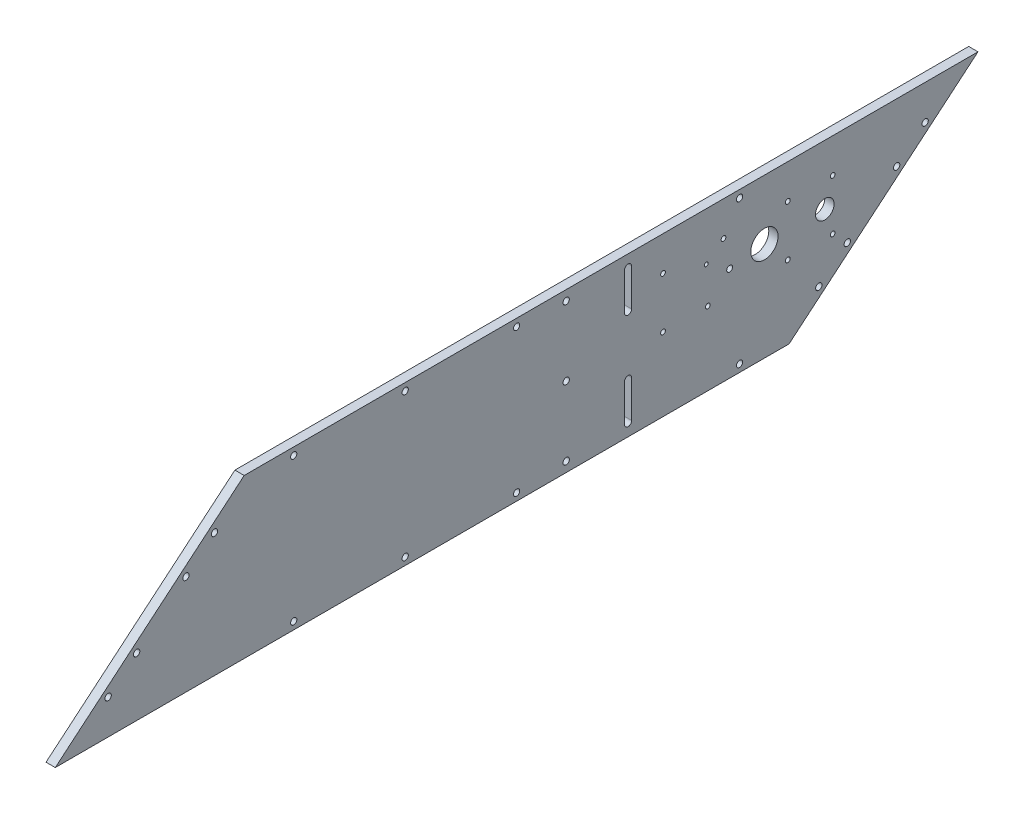
SolidWorks part; units mm, degrees
material "6061-T6 (SS)"
ref_plane "Front Plane" through (0, 0, 0) normal (0, 0, 1) x (1, 0, 0)
ref_plane "Top Plane" through (0, 0, 0) normal (0, 1, 0) x (1, 0, 0)
ref_plane "Right Plane" through (0, 0, 0) normal (1, 0, 0) x (0, 0, -1)
sketch "Sketch1" plane through (0, 0, 0) normal (1, 0, 0) x (0, 0, -1)
  line L0 (0, 12.7) -> (0, -12.7) construction
  line L1 (0, -12.7) -> (33.2976, -40.64) construction
  line L2 (33.2976, -40.64) -> (312.6976, -40.64)
  line L3 (312.6976, -40.64) -> (345.9952, -12.7)
  line L4 (345.9952, -12.7) -> (345.9952, 12.7) construction
  line L5 (345.9952, 12.7) -> (312.6976, 40.64) construction
  line L6 (312.6976, 40.64) -> (33.2976, 40.64)
  line L7 (33.2976, 40.64) -> (0, 12.7)
  line L8 (33.2976, 40.64) -> (33.2976, -40.64) construction
  line L9 (312.6976, 40.64) -> (312.6976, -40.64) construction
  line L10 (0, 0) -> (345.9952, 0) construction
  line L11 (0, 12.7) -> (-63.5681, -40.64)
  line L12 (-63.5681, -40.64) -> (33.2976, -40.64)
  line L13 (312.6976, 40.64) -> (409.5633, 40.64)
  line L14 (409.5633, 40.64) -> (345.9952, -12.7)
  point P10 (33.2976, 0)
  point P12 (312.6976, 0)
  dimension "D1" = 81.28
  dimension "D2" = 279.4
  dimension "D3" = 25.4
  dimension "D4" = 40
extrude "Boss-Extrude1" add sketch "Sketch1" along normal blind 4.7625
sketch "Sketch2" plane through (4.7625, 0, 0) normal (1, 0, 0) x (0, 0, -1)
  line L0 (-3.2177, 10) -> (373.048, 10) construction
  line L1 (312.6976, -40.64) -> (409.5633, 40.64) construction
  line L2 (345.048, 10) -> (245.048, 10) construction
  line L3 (245.048, -5) -> (345.048, -5) construction
  line L4 (245.048, -5) -> (245.048, 25) construction
  line L5 (245.048, 25) -> (345.048, 25) construction
  line L6 (345.048, -5) -> (345.048, 25) construction
  line L7 (0, 0) -> (361.1305, 0) construction
  line L9 (33.2976, 40.64) -> (-63.5681, -40.64) construction
  circle A0 centre (300.048, 10) radius 6.9977
  circle A1 centre (282.2147, 8) radius 1.4986
  circle A2 centre (270.2178, 15.9334) radius 0.9906
  circle A3 centre (282.2147, 8) radius 11.4777 construction
  circle A4 centre (270.2178, 15.9334) radius 7.1501 construction
  circle A5 centre (300.048, 10) radius 12.827 construction
  circle A6 centre (261.048, 10) radius 14 construction
  circle A7 centre (282.2147, 8) radius 5.1181 construction
  circle A8 centre (331.0042, 10) radius 4.7625
  point P11 (300.048, 10)
  point P12 (282.2147, 8)
  point P13 (270.2178, 15.9334)
  point P23 (261.048, 10)
  dimension "D5" = 13.9954
  dimension "D6" = 2.9972
  dimension "D7" = 1.9812
  dimension "D8" = 25.654
  dimension "D9" = 22.9553
  dimension "D10" = 14.3002
  dimension "D12" = 28
  dimension "D13" = 10.2362
  dimension "D17" = 9.525
  dimension "D1" = 17.9451
  dimension "D2" = 14.3828
  dimension "D3" = 30
  dimension "D4" = 100
  dimension "D11" = 10.922
  dimension "D14" = 16
  dimension "D15" = 13
  dimension "D16" = 55
  dimension "D18" = 30.9562
  dimension "D19" = 28
  dimension "D20" = 10
extrude "Gearbox (with Press fits)" cut sketch "Sketch2" against normal through all
sketch "Sketch6" plane through (4.7625, 0, 0) normal (1, 0, 0) x (0, 0, -1)
  line L0 (0, 0) -> (361.1305, 0) construction
  line L1 (230.1476, 36.83) -> (230.1476, -36.83) construction
  line L2 (28.757, 36.83) -> (405.0227, 36.83) construction
  line L3 (33.2976, 40.64) -> (-63.5681, -40.64) construction
  line L4 (230.1476, 34.29) -> (230.1476, 15.24) construction
  line L5 (409.5633, 40.64) -> (33.2976, 40.64) construction
  line L6 (312.6976, -40.64) -> (409.5633, 40.64) construction
  line L7 (231.9764, 34.29) -> (231.9764, 15.24)
  line L8 (228.3188, 34.29) -> (228.3188, 15.24)
  line L9 (409.5633, 40.64) -> (33.2976, 40.64) construction
  line L10 (230.1476, -34.29) -> (230.1476, -15.24) construction
  line L11 (231.9764, -34.29) -> (231.9764, -15.24)
  line L12 (228.3188, -34.29) -> (228.3188, -15.24)
  circle A0 centre (287.2976, 36.83) radius 1.5939
  circle A1 centre (230.1476, 36.83) radius 1.5939 construction
  circle A2 centre (172.9976, 36.83) radius 1.5939
  circle A3 centre (115.8476, 36.83) radius 1.5938
  circle A4 centre (58.6976, 36.83) radius 1.5938
  circle A5 centre (58.6976, -36.83) radius 1.5938
  circle A6 centre (115.8476, -36.83) radius 1.5938
  circle A7 centre (172.9976, -36.83) radius 1.5939
  circle A8 centre (230.1476, -36.83) radius 1.5939 construction
  circle A9 centre (287.2976, -36.83) radius 1.5939
  arc A10 (231.9764, 34.29) -> (228.3188, 34.29) centre (230.1476, 34.29) ccw
  arc A11 (228.3188, 15.24) -> (231.9764, 15.24) centre (230.1476, 15.24) ccw
  arc A12 (231.9764, -34.29) -> (228.3188, -34.29) centre (230.1476, -34.29) cw
  arc A13 (228.3188, -15.24) -> (231.9764, -15.24) centre (230.1476, -15.24) cw
  point P9 (230.1476, 24.765)
  point P43 (230.1476, -24.765)
  dimension "D2" = 3.1877
  dimension "D1" = 3.81
  dimension "D3" = 25.4
  dimension "D5" = 3.6576
  dimension "D6" = 6.35
  dimension "D7" = 19.05
  dimension "D4" = 5
extrude "Cut-Extrude2" cut sketch "Sketch6" against normal through all
hole_wizard "#4 Clearance Hole2" positions "Sketch8" profile "Sketch7" hole size "#4" standard "ANSI Inch" end condition through all
sketch "Sketch8" plane through (4.7625, 0, 0) normal (1, 0, 0) x (0, 0, -1)
  line L0 (0, 0) -> (361.1305, 0) construction
  line L1 (312.6976, -40.64) -> (409.5633, 40.64) construction
  line L3 (27.2435, 35.56) -> (403.5092, 35.56) construction
  line L4 (33.2976, 40.64) -> (-63.5681, -40.64) construction
  line L7 (198.3976, 35.56) -> (198.3976, -35.56) construction
  line L8 (409.5633, 40.64) -> (33.2976, 40.64) construction
  point P15 (198.3976, 35.56)
  point P18 (198.3976, -35.56)
  point P30 (198.3976, 0)
  dimension "D2" = 165.1
  dimension "D3" = 5.08
sketch "Sketch7" plane through (4.7625, 35.56, -198.3976) normal (0, 1, 0) x (0, 0, -1)
  line L0 (0, 0) -> (0, 4.7625)
  line L1 (0, 4.7625) -> (1.6319, 4.7625)
  line L2 (1.6319, 4.7625) -> (1.6319, 0)
  line L5 (1.6319, 0) -> (0, 0)
  line L11 (0, -6.35) -> (0, 107.95) construction
  dimension "Thru Hole Dia." = 3.2639
  dimension "Thru Hole Depth" = 4.7625
hole_wizard "#2 Clearance Hole1" positions "Sketch10" profile "Sketch9" hole size "#2" standard "ANSI Inch"
sketch "Sketch10" plane through (4.7625, 0, 0) normal (1, 0, 0) x (0, 0, -1)
  line L0 (245.048, 40.64) -> (245.048, -40.64) construction
  line L1 (409.5633, 40.64) -> (33.2976, 40.64) construction
  line L2 (-63.5681, -40.64) -> (312.6976, -40.64) construction
  line L4 (248.048, 40.64) -> (248.048, -40.64) construction
  line L6 (245.048, 23) -> (335.048, 23) construction
  line L8 (245.048, -6) -> (328.5196, -6) construction
  line L10 (245.048, -3) -> (335.048, -3) construction
  line L11 (312.048, 23) -> (312.048, -3) construction
  line L12 (373.048, 10) -> (261.048, 10) construction
  line L13 (312.6976, -40.64) -> (409.5633, 40.64) construction
  line L14 (331.0042, 10) -> (331.0042, 40.64) construction
  line L15 (335.048, 23) -> (335.048, -3) construction
  circle A0 centre (331.0042, 10) radius 4.7625 construction
  point P25 (248.048, -3)
  point P27 (248.048, 23)
  point P29 (271.048, -3)
  point P31 (312.048, -3)
  point P33 (279.048, 23)
  point P35 (312.048, 23)
  point P70 (335.048, 23)
  point P72 (335.048, -3)
  dimension "D1" = 3
  dimension "D2" = 3
  dimension "D3" = 26
  dimension "D4" = 34
  dimension "D5" = 67
  dimension "D6" = 29
  dimension "D7" = 69.9562
  dimension "D8" = 16
  dimension "D9" = 16
  dimension "D10" = 90
sketch "Sketch9" plane through (4.7625, -3, -248.048) normal (0, 1, 0) x (0, 0, -1)
  line L0 (0, 0) -> (0, 5.5586)
  line L1 (0, 5.5586) -> (1.2192, 4.826)
  line L2 (1.2192, 4.826) -> (1.2192, 0)
  line L5 (1.2192, 0) -> (0, 0)
  line L10 (0, 5.5586) -> (-1.2192, 4.826) construction
  line L11 (0, -6.35) -> (0, 107.95) construction
  dimension "Hole Dia." = 2.4384
  dimension "Hole Depth" = 4.826
  dimension "Drill Angle" = 118
hole_wizard "#4 Clearance Hole1" positions "Sketch12" profile "Sketch11" hole size "#4" standard "ANSI Inch"
sketch "Sketch12" plane through (4.7625, 0, 0) normal (1, 0, 0) x (0, 0, -1)
  line L9 (-15.1353, 0) -> (361.1305, 0) construction
  line L10 (33.2976, 40.64) -> (-63.5681, -40.64) construction
  line L11 (312.6976, -40.64) -> (409.5633, 40.64) construction
  line L13 (403.636, 40.64) -> (306.7703, -40.64) construction
  line L14 (409.5633, 40.64) -> (33.2976, 40.64) construction
  line L15 (-63.5681, -40.64) -> (312.6976, -40.64) construction
  line L17 (39.2249, 40.64) -> (-57.6408, -40.64) construction
  line L18 (355.2032, 0) -> (-9.208, 0) construction
  line L19 (-36.4485, -22.8575) -> (327.9626, -22.8575) construction
  line L21 (-21.8554, -10.6124) -> (342.5558, -10.6124) construction
  line L23 (3.4394, 10.6124) -> (367.8505, 10.6124) construction
  line L25 (18.0326, 22.8575) -> (382.4437, 22.8575) construction
  point P40 (327.9626, -22.8575)
  point P42 (342.5558, -10.6124)
  point P44 (367.8505, 10.6124)
  point P46 (382.4437, 22.8575)
  point P54 (-36.4485, -22.8575)
  point P56 (-21.8554, -10.6124)
  point P58 (3.4394, 10.6124)
  point P60 (18.0326, 22.8575)
  dimension "D1" = 16.51
  dimension "D2" = 19.05
  dimension "D3" = 16.51
  dimension "D4" = 19.05
  dimension "D5" = 3.81
  dimension "D6" = 3.81
sketch "Sketch11" plane through (4.7625, -22.8575, -327.9626) normal (0, 1, 0) x (0, 0, -1)
  line L0 (0, 0) -> (0, 5.8066)
  line L1 (0, 5.8066) -> (1.6319, 4.826)
  line L2 (1.6319, 4.826) -> (1.6319, 0)
  line L5 (1.6319, 0) -> (0, 0)
  line L10 (0, 5.8066) -> (-1.6319, 4.826) construction
  line L11 (0, -6.35) -> (0, 107.95) construction
  dimension "Hole Dia." = 3.2639
  dimension "Hole Depth" = 4.826
  dimension "Drill Angle" = 118
sketch "Sketch15" plane through (4.7625, 0, 0) normal (1, 0, 0) x (0, 0, -1)
  line L0 (217.2296, 27.94) -> (238.523, 27.94)
  line L1 (210.725, 16.7148) -> (232.0185, -23.2727)
  line L2 (204.7476, -24.765) -> (204.7476, 15.2225)
  line L3 (-28.6752, -27.94) -> (37.92, 27.94) construction
  line L4 (214.4271, 23.2727) -> (235.7206, -16.7148)
  line L5 (241.698, 24.765) -> (241.698, -15.2225)
  line L6 (229.216, -27.94) -> (207.9226, -27.94)
  line L7 (-48.4329, -27.94) -> (327.8329, -27.94) construction
  line L8 (33.2976, 40.64) -> (-63.5681, -40.64) construction
  line L9 (312.6976, -40.64) -> (409.5633, 40.64) construction
  line L10 (-63.5681, -40.64) -> (312.6976, -40.64) construction
  line L11 (18.1623, 27.94) -> (394.4281, 27.94) construction
  line L12 (409.5633, 40.64) -> (33.2976, 40.64) construction
  line L13 (35.7449, 26.1148) -> (-21.9928, -22.3328)
  line L14 (-19.9519, -27.94) -> (88.637, -27.94)
  line L15 (90.8271, -22.4663) -> (39.9758, 25.9814)
  line L16 (62.0768, 22.4663) -> (112.7937, -25.8534)
  line L17 (117.1739, -25.8534) -> (167.8909, 22.4663)
  line L18 (64.2668, 27.94) -> (165.7008, 27.94)
  line L19 (139.1405, -22.4663) -> (186.6825, 22.8285)
  line L20 (192.0476, 20.5298) -> (192.0476, -24.765)
  line L21 (188.8726, -27.94) -> (141.3306, -27.94)
  line L22 (114.9838, 27.94) -> (114.9838, -27.94) construction
  line L23 (254.398, 27.94) -> (254.398, -27.94) construction
  line L24 (254.398, -12.525) -> (254.398, -24.765)
  line L25 (257.573, -27.94) -> (306.9196, -27.94)
  line L26 (308.9604, -27.1972) -> (323.5475, -14.9572)
  line L27 (321.5066, -9.35) -> (257.573, -9.35)
  circle A0 centre (198.3976, 0) radius 6.35 construction
  circle A1 centre (198.3976, 35.56) radius 6.35 construction
  circle A2 centre (198.3976, -35.56) radius 6.35 construction
  circle A3 centre (248.048, -3) radius 6.35 construction
  arc A4 (204.7476, -24.765) -> (207.9226, -27.94) centre (207.9226, -24.765) ccw
  arc A5 (229.216, -27.94) -> (232.0185, -23.2727) centre (229.216, -24.765) ccw
  arc A6 (241.698, -15.2225) -> (235.7206, -16.7148) centre (238.523, -15.2225) cw
  arc A7 (238.523, 27.94) -> (241.698, 24.765) centre (238.523, 24.765) cw
  arc A8 (217.2296, 27.94) -> (214.4271, 23.2727) centre (217.2296, 24.765) ccw
  arc A9 (204.7476, 15.2225) -> (210.725, 16.7148) centre (207.9226, 15.2225) cw
  arc A10 (-21.9928, -22.3328) -> (-19.9519, -27.94) centre (-19.9519, -24.765) ccw
  arc A11 (186.6825, 22.8285) -> (192.0476, 20.5298) centre (188.8726, 20.5298) cw
  arc A12 (192.0476, -24.765) -> (188.8726, -27.94) centre (188.8726, -24.765) cw
  arc A13 (139.1405, -22.4663) -> (141.3306, -27.94) centre (141.3306, -24.765) ccw
  arc A14 (88.637, -27.94) -> (90.8271, -22.4663) centre (88.637, -24.765) ccw
  arc A15 (35.7449, 26.1148) -> (39.9758, 25.9814) centre (37.7857, 23.6826) cw
  arc A16 (112.7937, -25.8534) -> (117.1739, -25.8534) centre (114.9838, -23.5547) ccw
  arc A17 (167.8909, 22.4663) -> (165.7008, 27.94) centre (165.7008, 24.765) ccw
  arc A18 (62.0768, 22.4663) -> (64.2668, 27.94) centre (64.2668, 24.765) cw
  circle A19 centre (271.048, -3) radius 6.35 construction
  arc A20 (323.5475, -14.9572) -> (321.5066, -9.35) centre (321.5066, -12.525) ccw
  arc A21 (306.9196, -27.94) -> (308.9604, -27.1972) centre (306.9196, -24.765) ccw
  arc A22 (254.398, -24.765) -> (257.573, -27.94) centre (257.573, -24.765) ccw
  arc A23 (254.398, -12.525) -> (257.573, -9.35) centre (257.573, -12.525) cw
  point P15 (204.7476, -27.94)
  point P36 (241.698, -27.94)
  point P40 (204.7476, -27.94)
  point P59 (192.0476, 27.94)
  point P62 (192.0476, -27.94)
  point P65 (133.3952, -27.94)
  point P68 (96.5724, -27.94)
  point P77 (173.6362, 27.94)
  point P80 (56.3315, 27.94)
  point P82 (204.7476, 27.94)
  point P95 (308.0752, -27.94)
  point P101 (254.398, -9.35)
  dimension "D1" = 12.7
  dimension "D2" = 12.7
  dimension "D3" = 12.7
  dimension "D4" = 12.7
  dimension "D8" = 3.175
  dimension "D12" = 3.175
  dimension "D13" = 12.7
  dimension "D15" = 3.175
  dimension "D5" = 12.7
  dimension "D6" = 12.7
  dimension "D7" = 6.35
  dimension "D9" = 12.7
  dimension "D10" = 12.7
  dimension "D11" = 12.7
  dimension "D14" = 12.7
extrude "Cut-Extrude3" [suppressed] cut sketch "Sketch15" against normal through all
